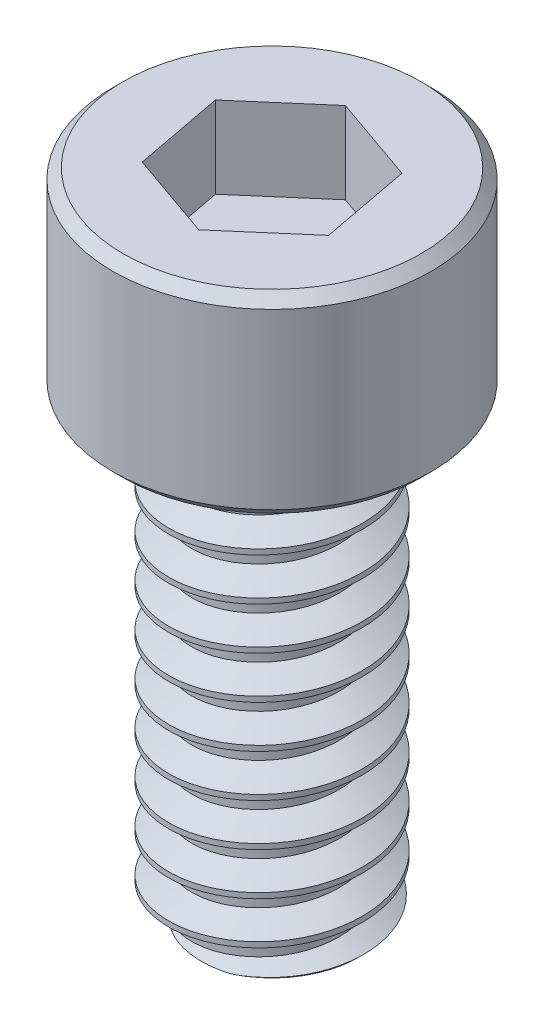
SolidWorks part; units mm, degrees
ref_plane "Front Plane" through (0, 0, 0) normal (0, 0, 1) x (1, 0, 0)
ref_plane "Top Plane" through (0, 0, 0) normal (0, 1, 0) x (1, 0, 0)
ref_plane "Right Plane" through (0, 0, 0) normal (1, 0, 0) x (0, 0, -1)
sketch "Sketch1" plane through (0, 0, 0) normal (0, 1, 0) x (1, 0, 0)
  circle A0 centre (0, 0) radius 3.9624
  dimension "D1" = 7.9248
extrude "Boss-Extrude1" add sketch "Sketch1" along normal blind 4.826
sketch "Sketch2" plane through (0, 4.826, 0) normal (0, 1, 0) x (1, 0, 0)
  line L1 (1.736, 1.4955) -> (-0.4271, 2.2512)
  line L2 (-0.4271, 2.2512) -> (-2.1632, 0.7557)
  line L3 (-2.1632, 0.7557) -> (-1.736, -1.4955)
  line L4 (-1.736, -1.4955) -> (0.4271, -2.2512)
  line L5 (0.4271, -2.2512) -> (2.1632, -0.7557)
  line L6 (2.1632, -0.7557) -> (1.736, 1.4955)
  circle A0 centre (0, 0) radius 1.9844 construction
  circle A1 centre (0, 0) radius 3.9624 construction
  dimension "D1" = 3.9688
  dimension "D2" = 0.4271
extrude "Cut-Extrude1" cut sketch "Sketch2" against normal blind 2.032
sketch "Sketch3" plane through (0, 0, 0) normal (0, -1, 0) x (1, 0, 0)
  circle A0 centre (0, 0) radius 2.413
  dimension "D1" = 4.826
extrude "Boss-Extrude2" add sketch "Sketch3" along normal blind 11.1125
chamfer "Chamfer1" distance 0.254 angle 45 2 edges at (0, 4.826, 3.9624) (0, 0, 3.9624)
thread "Thread1" pitch 1.0583 start angle 0, offset 1.27, length 0, pitch 1.0583, diameter 4.826
ref_plane "Plane1" through (2.413, -12.1285, 0) normal (0, 0, 1) x (1, 0, 0)
sketch "Thread Profile1" plane through (2.413, -12.1285, 0) normal (0, 0, 1) x (1, 0, 0)
  line L0 (0, 0) -> (0, 1.0583) construction
  line L11 (0, 0) -> (0, 0.926)
  line L12 (0, 0.926) -> (-0.5728, 0.5953)
  line L13 (-0.5728, 0.5953) -> (-0.5728, 0.3307)
  line L15 (-0.5728, 0.3307) -> (0, 0)
  line L17 (-0.5728, 0.463) -> (0, 0.463) construction
  point P2 (0, 0)
  dimension "Pitch" = 1.0583
  dimension "Profile_Angle" = 60
  dimension "Profile_Land" = 0.2646
  dimension "Profile_Height" = 0.5728
